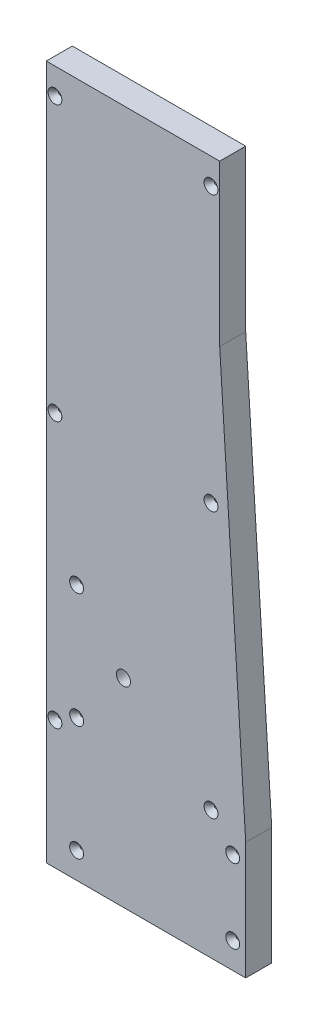
SolidWorks part; units mm, degrees
material "MDF"
ref_plane "Front Plane" through (0, 0, 0) normal (0, 0, 1) x (1, 0, 0)
ref_plane "Top Plane" through (0, 0, 0) normal (0, 1, 0) x (1, 0, 0)
ref_plane "Right Plane" through (0, 0, 0) normal (1, 0, 0) x (0, 0, -1)
sketch "Sketch1" plane through (0, 0, 0) normal (0, 0, 1) x (1, 0, 0)
  line L0 (82.0395, -5024.8784) -> (82.0395, -5533.4155)
  line L1 (82.0395, -5024.8784) -> (82.0395, -5464.9635) construction
  line L8 (-209.0395, -5024.8784) -> (-209.0395, -5142.5528)
  line L11 (-228.0888, -5533.4155) -> (228.0888, -5533.4155)
  line L14 (209.0395, -5142.5528) -> (209.0395, -5024.8784)
  line L15 (209.0395, -5024.8784) -> (-209.0395, -5024.8784)
  line L22 (209.0395, -5142.5528) -> (209.0395, -5024.8784)
  line L23 (209.0395, -5024.8784) -> (82.0395, -5024.8784)
  line L106 (82.0395, -5533.4155) -> (228.0888, -5533.4155)
  line L119 (-209.0395, -5142.5528) -> (-228.0888, -5447.3417)
  line L120 (-228.0888, -5447.3417) -> (-228.0888, -5533.4155)
  line L121 (228.0888, -5533.4155) -> (228.0888, -5447.3417)
  line L122 (228.0888, -5533.4155) -> (228.0888, -5447.3417)
  line L123 (228.0888, -5447.3417) -> (209.0395, -5142.5528)
  line L124 (228.0888, -5447.3417) -> (209.0395, -5142.5528)
  dimension "D1" = 0
extrude "Boss-Extrude1" add sketch "Sketch1" along normal blind 19.05
hole_wizard "3/8 Clearance Hole1" positions "Sketch2" profile "Sketch4" hole size "3/8" standard "ANSI Inch" end condition through all
sketch "Sketch2" plane through (0, 0, 19.05) normal (0, 0, 1) x (1, 0, 0)
  point P9 (138.551, -5387.9638)
sketch "Sketch4" plane through (138.551, -5387.9638, 19.05) normal (1, 0, 0) x (0, -1, 0)
  line L0 (0, 0) -> (0, 19.05)
  line L1 (0, 19.05) -> (5.1587, 19.05)
  line L2 (5.1587, 19.05) -> (5.1587, 0)
  line L5 (5.1587, 0) -> (0, 0)
  line L11 (0, -6.35) -> (0, 107.95) construction
  dimension "Thru Hole Dia." = 10.3175
  dimension "Thru Hole Depth" = 19.05
hole_wizard "Hole1" positions "Sketch5" profile "Sketch6" legacy
sketch "Sketch5" plane through (0, -5562.8703, 19.05) normal (0, 0, 1) x (1, 0, 0)
  line L0 (218.5638, 29.4548) -> (218.5638, 115.5175) construction
  line L4 (202.6895, 537.9919) -> (202.6895, 97.9067) construction
  line L9 (88.3895, 537.9919) -> (88.3895, 97.9067) construction
  line L13 (104.2638, 29.4548) -> (104.2638, 235.8996) construction
  line L16 (0, 537.9919) -> (0, 29.4548) construction
  point P0 (218.5638, 102.8175)
  point P2 (218.5638, 48.5048)
  point P33 (202.6895, 123.3067)
  point P35 (202.6895, 317.9493)
  point P37 (202.6895, 518.9419)
  point P51 (88.3895, 518.9419)
  point P53 (88.3895, 317.9493)
  point P55 (88.3895, 123.3067)
  point P69 (104.2638, 216.8496)
  point P71 (104.2638, 132.6772)
  point P73 (104.2638, 48.5048)
  point P83 (-104.2638, 48.5048)
  point P84 (-104.2638, 132.6772)
  point P85 (-104.2638, 216.8496)
  point P86 (-88.3895, 123.3067)
  point P87 (-88.3895, 317.9493)
  point P88 (-88.3895, 518.9419)
  point P89 (-202.6895, 518.9419)
  point P90 (-202.6895, 317.9493)
  point P91 (-202.6895, 123.3067)
  point P92 (-218.5638, 48.5048)
  point P93 (-218.5638, 102.8175)
sketch "Sketch6" plane through (218.5638, -5460.0528, 19.05) normal (1, 0, 0) x (0, -1, 0)
  line L0 (0, 0) -> (0, 51.7539)
  line L1 (0, 51.7539) -> (1.5875, 50.8)
  line L2 (1.5875, 50.8) -> (1.5875, 4.0177)
  line L3 (1.5875, 4.0177) -> (5.08, 0)
  line L4 (5.08, 0) -> (0, 0)
  line L5 (0, -14.3089) -> (0, 102.4216) construction
  line L6 (0, 51.7539) -> (-1.5875, 50.8) construction
  line L7 (-1.5875, 4.0177) -> (-5.08, 0) construction
  dimension "Diameter" = 3.175
  dimension "Depth" = 50.8
  dimension "C-Sink Diameter" = 10.16
  dimension "C-Sink Angle" = 82
  dimension "Drill Angle" = 118
